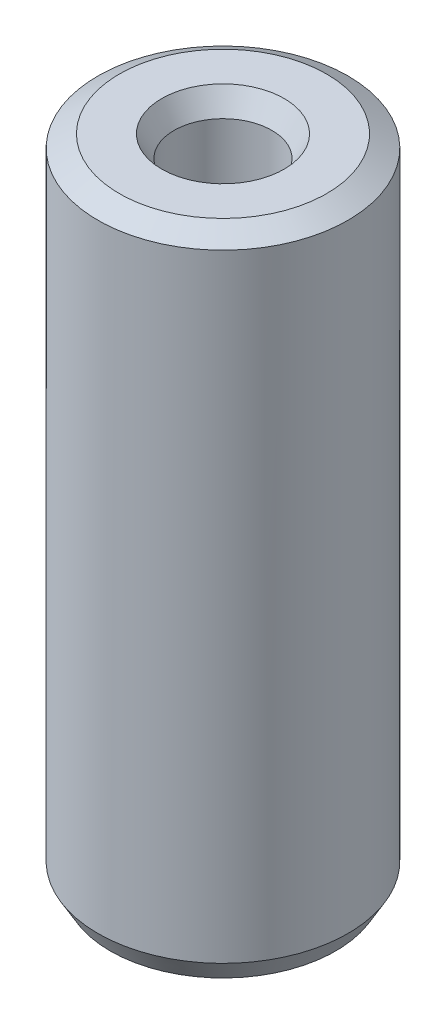
SolidWorks part; units mm, degrees
ref_plane "Front Plane" through (0, 0, 0) normal (0, 0, 1) x (1, 0, 0)
ref_plane "Top Plane" through (0, 0, 0) normal (0, 1, 0) x (1, 0, 0)
ref_plane "Right Plane" through (0, 0, 0) normal (1, 0, 0) x (0, 0, -1)
sketch "Sketch1" plane through (0, 0, 0) normal (0, 1, 0) x (1, 0, 0)
  circle A0 centre (0, 0) radius 32.5
  dimension "SLEEVE_OD" = 65
extrude "Boss-Extrude1" add sketch "Sketch1" along normal blind 169.2903
sketch "Sketch2" plane through (0, 0, 0) normal (0, 1, 0) x (1, 0, 0)
  circle A0 centre (0, 0) radius 12.6997
  dimension "BORE_D" = 25.3994
extrude "Cut-Extrude1" cut sketch "Sketch2" along normal through all
chamfer "Chamfer1" distance 3.2121 angle 60 4 edges at (0, 169.2903, 12.6997) (0, 0, 12.6997) (0, 0, 32.5) (0, 169.2903, 32.5) first distance on face at (0, 169.2903, 12.6997) first distance on face at (0, 0, 12.6997) first distance on face at (0, 169.2903, 32.5)
